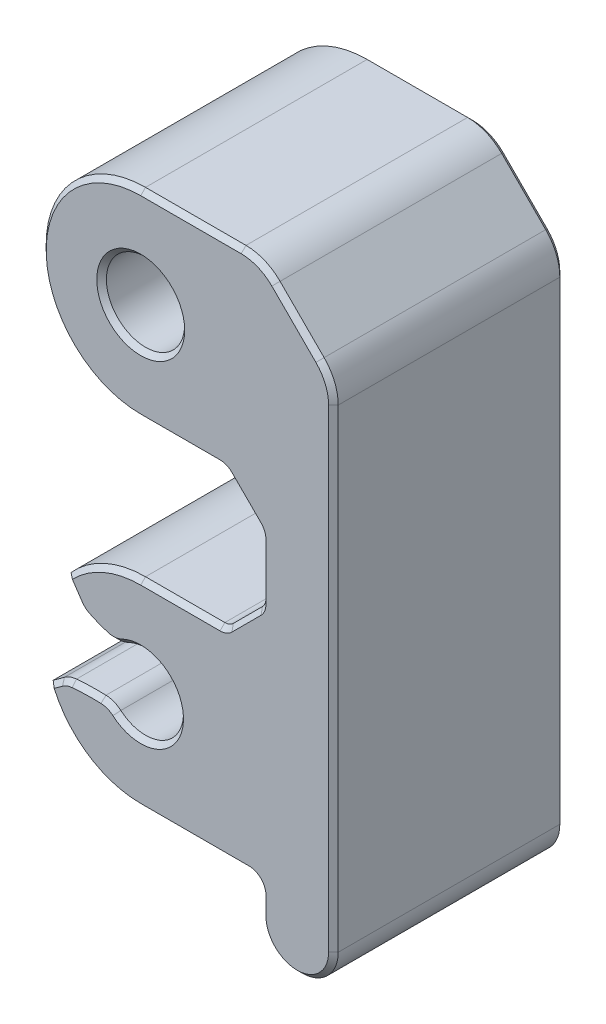
SolidWorks part; units mm, degrees
ref_plane "Front" through (0, 0, 0) normal (0, 0, 1) x (1, 0, 0)
ref_plane "Top" through (0, 0, 0) normal (0, 1, 0) x (1, 0, 0)
ref_plane "Right" through (0, 0, 0) normal (1, 0, 0) x (0, 0, -1)
sketch "Sketch2" plane through (0, 0, 0) normal (0, 0, 1) x (1, 0, 0)
  line L0 (0, 1.625) -> (0, 4.125) construction
  line L4 (8, -15.125) -> (8, 1.125)
  line L6 (0, 4.125) -> (5, 4.125)
  line L7 (5, 4.125) -> (8, 1.125)
  line L8 (8, -15.125) -> (5, -18.125)
  line L9 (5, -18.125) -> (0, -18.125)
  line L10 (0, -9.875) -> (3.5, -9.875)
  line L11 (3.5, -9.875) -> (5, -8.375)
  line L12 (5, -8.375) -> (5, -5.625)
  line L13 (5, -5.625) -> (3.5, -4.125)
  line L14 (3.5, -4.125) -> (0, -4.125)
  circle A0 centre (0, 0) radius 1.575 construction
  circle A1 centre (0, 0) radius 4.125 construction
  circle A2 centre (0, -14) radius 1.575
  circle A3 centre (0, -14) radius 4.125 construction
  arc A4 (0, 4.125) -> (0, -4.125) centre (0, 0) ccw
  arc A5 (0, -18.125) -> (0, -9.875) centre (0, -14) cw
  circle A6 centre (0, 0) radius 1.625
  dimension "D1" = 3.15
  dimension "D2" = 2.5
  dimension "D3" = 14
  dimension "D4" = 45
  dimension "D6" = 45
  dimension "D7" = 1.5
  dimension "D8" = 3
  dimension "D9" = 8
  dimension "D10" = 3
  dimension "D5" = 0.05
extrude "Boss-Extrude1" add sketch "Sketch2" along normal mid plane 10
sketch "Sketch3" plane through (0, 0, 0) normal (0, 0, 1) x (1, 0, 0)
  line L0 (-5.1894, -13.0534) -> (-4.352, -10.3117)
  line L1 (-5.1894, -13.0534) -> (-6.0268, -15.7952)
  line L2 (0, -15.15) -> (0, -12.85)
  circle A0 centre (0, 0) radius 14 construction
  arc A1 (-4.0896, -13.3894) -> (0, -14) centre (0, 0) ccw construction
  arc A2 (-4.4255, -14.4892) -> (0, -15.15) centre (0, 0) ccw construction
  arc A3 (-3.7537, -12.2895) -> (0, -12.85) centre (0, 0) ccw construction
  arc A4 (-3.7537, -12.2895) -> (-4.4255, -14.4892) centre (-4.0896, -13.3894) ccw construction
  arc A5 (0, -15.15) -> (0, -12.85) centre (0, -14) ccw construction
  arc A6 (0, -9.875) -> (0, -18.125) centre (0, -14) ccw construction
  arc A7 (0, -12.85) -> (-4.352, -10.3117) centre (0, -7.85) cw
  arc A8 (0, -15.15) -> (-6.0268, -15.7952) centre (-1.9991, -24.9481) ccw
  point P5 (-2.0675, -13.8465)
  dimension "D1" = 1.15
  dimension "D2" = 5
  dimension "D3" = 10
extrude "Latch Notch" cut sketch "Sketch3" against normal through all both and the other way through all
chamfer "Chamfer1" distance 0.4 angle 70 2 edges at (-3.9635, -15.143, 0) (-3.3363, -11.5741, 0) first distance on face at (-2.2309, -16.9651, 0) first distance on face at (-1.7701, -10.5244, 0)
fillet "Fillet2" radius 1 4 edges at (-1.2351, -14.9774, 0) (-0.9658, -12.7558, 0) (-2.4587, -12.2037, 0) (-3.149, -15.0145, 0)
sketch "Sketch4" plane through (0, 0, 0) normal (0, 0, 1) x (1, 0, 0)
  line L0 (8, -10.1681) -> (12.5426, -14.7108)
  line L1 (9.7142, -17.5392) -> (7.65, -15.475)
  line L4 (8, -10.1681) -> (7.65, -15.475)
  line L5 (8, -15.125) -> (8, 1.125) construction
  line L6 (5, -18.125) -> (8, -15.125) construction
  line L7 (5, -18.125) -> (0, -18.125) construction
  line L8 (8, -15.125) -> (8, 1.125) construction
  line L9 (8, -15.125) -> (5, -18.125) construction
  arc A2 (12.5426, -14.7108) -> (9.7142, -17.5392) centre (11.1284, -16.125) cw
  dimension "D1" = 2
  dimension "D2" = 0.35
extrude "Thumb Bump Short" [suppressed] add sketch "Sketch4" along normal through all and the other way through all
fillet "Fillet5" [suppressed] radius 0.5
fillet "Fillet1" [suppressed] radius 0.5
sketch "Sketch6" plane through (0, 0, 0) normal (0, 0, 1) x (1, 0, 0)
  line L0 (8, -15.125) -> (8, -19.375)
  line L1 (5, -19.375) -> (5, -18.125)
  line L2 (8, -15.125) -> (5, -18.125)
  arc A0 (8, -19.375) -> (5, -19.375) centre (6.5, -19.375) cw
  dimension "D1" = 1.25
extrude "Thumb Bump LONG" add sketch "Sketch6" along normal up to surface and the other way up to surface up to face at (1.625, 0, 5) other way up to face at (1.625, 0, -5)
fillet "Fillet6" radius 0.5 1 edges at (5, -18.125, 0)
sketch "Sketch5" plane through (0, 0, 5) normal (0, 0, 1) x (1, 0, 0)
  line L5 (-3.3677, -15.1738) -> (-3.8365, -15.5156)
  line L9 (-3.0899, -11.2672) -> (-2.5985, -11.9963)
  line L10 (-3.3677, -15.1738) -> (-3.8365, -15.5156)
  line L14 (-3.0899, -11.2672) -> (-2.5985, -11.9963)
  line L22 (5, -18.625) -> (5, -19.375)
  line L23 (5, -18.625) -> (5, -19.375)
  line L26 (0, -18.125) -> (4.5, -18.125)
  line L29 (8, -19.375) -> (8, 1.125)
  line L30 (8, -19.375) -> (8, 1.125)
  line L31 (8, 1.125) -> (5, 4.125)
  line L32 (8, 1.125) -> (5, 4.125)
  line L33 (5, 4.125) -> (0, 4.125)
  line L34 (5, 4.125) -> (0, 4.125)
  line L35 (0, -4.125) -> (3.5, -4.125)
  line L36 (0, -4.125) -> (3.5, -4.125)
  line L37 (3.5, -4.125) -> (5, -5.625)
  line L38 (3.5, -4.125) -> (5, -5.625)
  line L39 (5, -5.625) -> (5, -8.375)
  line L40 (5, -5.625) -> (5, -8.375)
  line L41 (5, -8.375) -> (3.5, -9.875)
  line L42 (5, -8.375) -> (3.5, -9.875)
  line L43 (3.5, -9.875) -> (0, -9.875)
  line L44 (3.5, -9.875) -> (0, -9.875)
  line L47 (0, -18.125) -> (4.5, -18.125)
  arc A7 (-1.6414, -14.9545) -> (-2.8653, -14.9857) centre (-1.9991, -24.9481) ccw
  arc A8 (-3.8365, -15.5156) -> (0, -18.125) centre (0, -14) ccw
  arc A10 (0, 4.125) -> (0, -4.125) centre (0, 0) ccw
  arc A11 (0, -9.875) -> (-3.0899, -11.2672) centre (0, -14) ccw
  arc A12 (-2.2115, -12.3343) -> (-1.4139, -12.6459) centre (0, -7.85) ccw
  arc A13 (-1.0258, -15.1951) -> (-0.6919, -12.5851) centre (0, -14) ccw
  arc A14 (-1.6414, -14.9545) -> (-2.8653, -14.9857) centre (-1.9991, -24.9481) ccw
  arc A15 (-3.8365, -15.5156) -> (0, -18.125) centre (0, -14) ccw
  arc A17 (0, 4.125) -> (0, -4.125) centre (0, 0) ccw
  arc A18 (0, -9.875) -> (-3.0899, -11.2672) centre (0, -14) ccw
  arc A19 (-2.2115, -12.3343) -> (-1.4139, -12.6459) centre (0, -7.85) ccw
  arc A20 (-1.0258, -15.1951) -> (-0.6919, -12.5851) centre (0, -14) ccw
  arc A27 (5, -18.625) -> (4.5, -18.125) centre (4.5, -18.625) ccw
  arc A31 (-1.4139, -12.6459) -> (-0.6919, -12.5851) centre (-1.1311, -11.6867) ccw
  arc A32 (-1.4139, -12.6459) -> (-0.6919, -12.5851) centre (-1.1311, -11.6867) ccw
  arc A33 (-1.0258, -15.1951) -> (-1.6414, -14.9545) centre (-1.6772, -15.9539) ccw
  arc A35 (-1.0258, -15.1951) -> (-1.6414, -14.9545) centre (-1.6772, -15.9539) ccw
  arc A37 (-2.5985, -11.9963) -> (-2.2115, -12.3343) centre (-1.7692, -11.4375) ccw
  arc A38 (-2.5985, -11.9963) -> (-2.2115, -12.3343) centre (-1.7692, -11.4375) ccw
  arc A39 (-2.8653, -14.9857) -> (-3.3677, -15.1738) centre (-2.7787, -15.982) ccw
  arc A40 (-2.8653, -14.9857) -> (-3.3677, -15.1738) centre (-2.7787, -15.982) ccw
  arc A51 (5, -18.625) -> (4.5, -18.125) centre (4.5, -18.625) ccw
  arc A55 (5, -19.375) -> (8, -19.375) centre (6.5, -19.375) ccw
  arc A56 (5, -19.375) -> (8, -19.375) centre (6.5, -19.375) ccw
  dimension "D1" = 0
extrude "Movement Clearance" cut sketch "Sketch5" against normal blind 0.2
mirror "Movement Clearance 2" about plane through (0, 0, 0) normal (0, 0, 1) of "Movement Clearance"
fillet "Fillet3" radius 2 2 edges at (8, 1.125, 0) (5, 4.125, 0)
fillet "Fillet7" [suppressed] radius 2
fillet "Fillet4" radius 0.5 4 edges at (3.5, -9.875, 0) (5, -8.375, 0) (5, -5.625, 0) (3.5, -4.125, 0)
chamfer "Chamfer2" distance 0.2 angle 45 62 edges at (-2.2538, -14.9514, -4.8) (-3.6021, -15.3447, -4.8) (-4.125, 0, -4.8) (-1.6945, -10.2391, -4.8) (-2.8442, -11.6318, -4.8) (-1.8194, -12.5072, -4.8) (1.5623, -14.1999, -4.8) (-1.8194, -12.5072, 4.8) (-2.8442, -11.6318, 4.8) (-1.6945, -10.2391, 4.8) (-4.125, 0, 4.8) (-3.6021, -15.3447, 4.8) (-2.2538, -14.9514, 4.8) (1.5623, -14.1999, 4.8) (-1.625, 0, -4.8) (1.625, 0, 4.8) (-1.0472, -12.6832, -4.8) (-1.3132, -15.0225, -4.8) (-1.3132, -15.0225, 4.8) (-1.0472, -12.6832, 4.8) (-2.4271, -12.1906, -4.8) (-3.1293, -15.0455, -4.8) (-3.1293, -15.0455, 4.8) (-2.4271, -12.1906, 4.8) (2.25, -18.125, -4.8) (8, -9.5392, -4.8) (6.5, 2.625, -4.8) (2.0858, 4.125, -4.8) (1.6464, -4.125, -4.8) (4.25, -4.875, -4.8) (5, -7, -4.8) (4.25, -9.125, -4.8) (1.6464, -9.875, -4.8) (1.6464, -9.875, 4.8) (4.25, -9.125, 4.8) (5, -7, 4.8) (4.25, -4.875, 4.8) (1.6464, -4.125, 4.8) (2.0858, 4.125, 4.8) (6.5, 2.625, 4.8) (8, -9.5392, 4.8) (2.25, -18.125, 4.8) (7.8478, 1.0619, -4.8) (4.9369, 3.9728, -4.8) (3.4842, -4.1631, -4.8) (4.9619, -5.6408, -4.8) (4.9619, -8.3592, -4.8) (3.4842, -9.8369, -4.8) (3.4842, -9.8369, 4.8) (4.9619, -8.3592, 4.8) (4.9619, -5.6408, 4.8) (3.4842, -4.1631, 4.8) (4.9369, 3.9728, 4.8) (7.8478, 1.0619, 4.8) (-2.3199, -17.4108, -4.8) (-2.3199, -17.4108, 4.8) (4.8536, -18.2714, -4.8) (5, -19, -4.8) (6.5, -20.875, -4.8) (6.5, -20.875, 4.8) (5, -19, 4.8) (4.8536, -18.2714, 4.8)
equation "\"D1@Sketch2\"=\"Hardware Clearance Hole Diameter@Box Assy.Assembly\""
